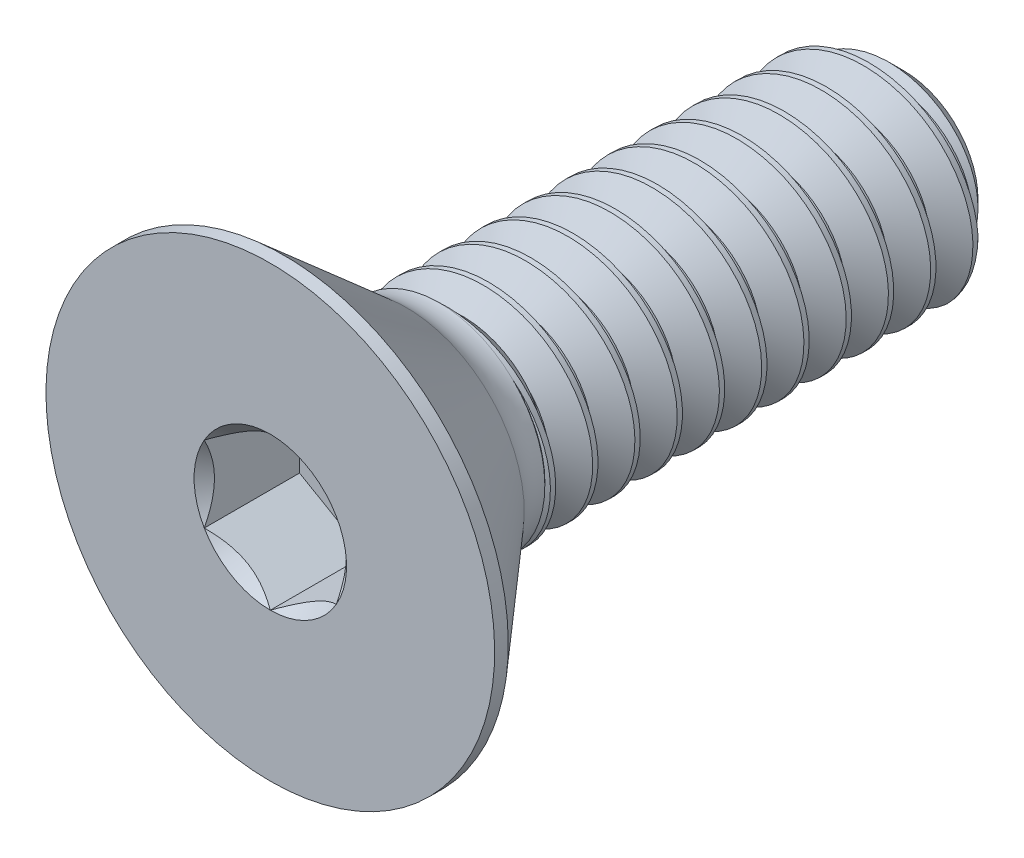
SolidWorks part; units mm, degrees
ref_plane "Front" through (0, 0, 0) normal (0, 0, 1) x (1, 0, 0)
ref_plane "Top" through (0, 0, 0) normal (0, 1, 0) x (1, 0, 0)
ref_plane "Right" through (0, 0, 0) normal (1, 0, 0) x (0, 0, -1)
sketch "Sketch1" plane through (0, 0, 0) normal (1, 0, 0) x (0, 0, -1)
  line L0 (0, 6.7437) -> (0.4089, 6.7437) construction
  line L1 (0.4089, 6.7437) -> (4.0894, 3.5443) construction
  line L2 (0, 3.175) -> (19.05, 3.175)
  line L3 (19.05, 3.175) -> (19.05, 0)
  line L4 (19.05, 0) -> (0, 0)
  line L5 (0, 0) -> (0, 6.7437) construction
  line L6 (0, 6.7437) -> (0, -6.7437) construction
  line L7 (19.05, 3.175) -> (19.05, -3.175) construction
  line L8 (0, -6.7437) -> (0.4089, -6.7437) construction
  line L9 (0.4089, -6.7437) -> (4.0894, -3.5443) construction
  line L11 (0, 3.175) -> (0, 0)
  line L12 (5.0772, 3.175) -> (5.0772, 0) construction
  arc A1 (4.0894, 3.5443) -> (5.0772, 3.175) centre (5.0772, 4.6807) ccw construction
  dimension "D1" = 0.4089
  dimension "Head Ht" = 4.0894
  dimension "Head Dia" = 13.4874
  dimension "Dia" = 6.35
  dimension "Lg" = 19.05
  dimension "Head Angle" = 82
revolve "Revolve1" add sketch "Sketch1" angle 360 about L4
sketch "Sketch3" plane through (0, 0, -19.05) normal (0, 0, -1) x (-1, 0, 0)
  circle A0 centre (0, 0) radius 3.175
curve "Helix/Spiral1" pitch 1.27 height 19.05 radius 3.175 centre (0, 0, -19.05) axis (0, 0, 1) start towards (0, 1, 0)
sketch "Sketch2" plane through (0, 0, 0) normal (1, 0, 0) x (0, 0, -1)
  line L0 (19.05, 3.175) -> (20.1612, 3.175)
  line L1 (20.1612, 3.175) -> (19.685, 2.3501)
  line L2 (19.685, 2.3501) -> (19.5262, 2.3501)
  line L3 (19.5262, 2.3501) -> (19.05, 3.175)
  line L4 (19.2881, 2.7626) -> (19.9231, 2.7626) construction
  dimension "D1" = 60
  dimension "D2" = 0.1588
  dimension "D3" = 0.635
chamfer "Chamfer1" distance 0.9525 angle 45 1 edges at (0, 3.175, -19.05)
sweep "Cut-Sweep1" cut profiles "Sketch2" path "Helix/Spiral1"
sketch "Sketch7" plane through (0, 0, 0) normal (1, 0, 0) x (0, 0, -1)
  line L0 (0, 6.7437) -> (0.4089, 6.7437) construction
  line L1 (0.4089, 6.7437) -> (4.0894, 3.5443) construction
  line L2 (0, 6.7437) -> (0.4089, 6.7437)
  line L3 (0.4089, 6.7437) -> (4.0894, 3.5443)
  line L4 (5.0772, 3.175) -> (5.0772, 0) construction
  line L5 (5.0772, 3.175) -> (5.0772, 0)
  line L7 (0, 0) -> (0, 6.7437) construction
  line L8 (0, 0) -> (0, 6.7437)
  line L9 (0, 0) -> (5.0772, 0)
  line L10 (7.4181, 0) -> (-7.4181, 0) construction
  arc A0 (4.0894, 3.5443) -> (5.0772, 3.175) centre (5.0772, 4.6807) ccw construction
  arc A1 (4.0894, 3.5443) -> (5.0772, 3.175) centre (5.0772, 4.6807) ccw
revolve "Revolve2" add sketch "Sketch7" angle 360 about L9
ref_plane "Plane1" through (0, 0, -5.0772) normal (0, 0, 1) x (1, 0, 0)
sketch "Sketch8" plane through (0, 0, -5.0772) normal (0, 0, 1) x (1, 0, 0)
  circle A0 centre (0, 0) radius 3.175
extrude "Boss-Extrude1" add sketch "Sketch8" against normal through all draft 45
sketch "Sketch11" [suppressed] plane through (0, 0, 0) normal (1, 0, 0) x (0, 0, -1)
  line L0 (4.4996, 0) -> (-4.4996, 0) construction
  line L1 (7.3025, 3.8989) -> (1.7272, 3.8989)
  line L2 (7.3025, 3.8989) -> (7.3025, -3.8989)
  line L3 (7.3025, -3.8989) -> (1.7272, -3.8989)
  line L4 (1.7272, 3.8989) -> (1.7272, -3.8989)
  line L5 (0, 3.8989) -> (0.1727, 3.8989) construction
  line L7 (4.7625, 1.7526) -> (4.7625, 0) construction
  point P4 (1.7272, 0)
  dimension "D1" = 2.54
extrude "Cut-Extrude4" [suppressed] cut sketch "Sketch11" against normal through all and the other way through all
combine bodies "Combine1" operation type add bodies to combine 117 114
sketch "Sketch5" plane through (0, 0, 0) normal (0, 0, 1) x (1, 0, 0)
  line L1 (1.9844, -1.1457) -> (1.9844, 1.1457)
  line L2 (1.9844, 1.1457) -> (0, 2.2914)
  line L3 (0, 2.2914) -> (-1.9844, 1.1457)
  line L4 (-1.9844, 1.1457) -> (-1.9844, -1.1457)
  line L5 (-1.9844, -1.1457) -> (0, -2.2914)
  line L6 (0, -2.2914) -> (1.9844, -1.1457)
  circle A0 centre (0, 0) radius 1.9844 construction
  dimension "Hex" = 3.9688
extrude "Cut-Extrude2" cut sketch "Sketch5" against normal blind 2.8626
sketch "Sketch6" plane through (0, 0, 0) normal (0, 0, 1) x (1, 0, 0)
  circle A0 centre (0, 0) radius 2.2914
extrude "Cut-Extrude3" cut sketch "Sketch6" against normal blind 2.8626 draft 45
sketch "Sketch9" [suppressed] plane through (0, 0, -5.0772) normal (0, 0, 1) x (1, 0, 0)
  circle A1 centre (0, 0) radius 3.175
  circle A2 centre (0, 0) radius 3.175
  point P0 (0, 3.175)
  dimension "D1" = 0
extrude "Boss-Extrude2" [suppressed] add sketch "Sketch9" against normal offset from surface (20.3228 mm away) 44.45 up to face at (0, 2.2225, -19.05)
sketch "Sketch10" plane through (0, 0, 0) normal (1, 0, 0) x (0, 0, -1)
  line L0 (19.05, 3.175) -> (19.05, -3.175) construction
  point P0 (17.145, -3.175)
  dimension "D1" = 1.905
equation "\"D3@Helix/Spiral1\" = \"Lg@Sketch1\""
equation "\"D2@Sketch2\" = \"D4@Helix/Spiral1\" * .125"
equation "\"D3@Sketch2\" = \"D4@Helix/Spiral1\" * .5"
equation "\"D1@Chamfer1\" = \"D4@Helix/Spiral1\" * .75"
equation "\"D1@Cut-Extrude2\" = \"Head Ht@Sketch1\" * .7"
equation "\"D1@Sketch1\" = \"Head Ht@Sketch1\" * .1"
equation "\"D1@Sketch10\" = \"D4@Helix/Spiral1\" * 1.5"
equation "\"D1@Cut-Extrude3\" = \"D1@Cut-Extrude2\""
